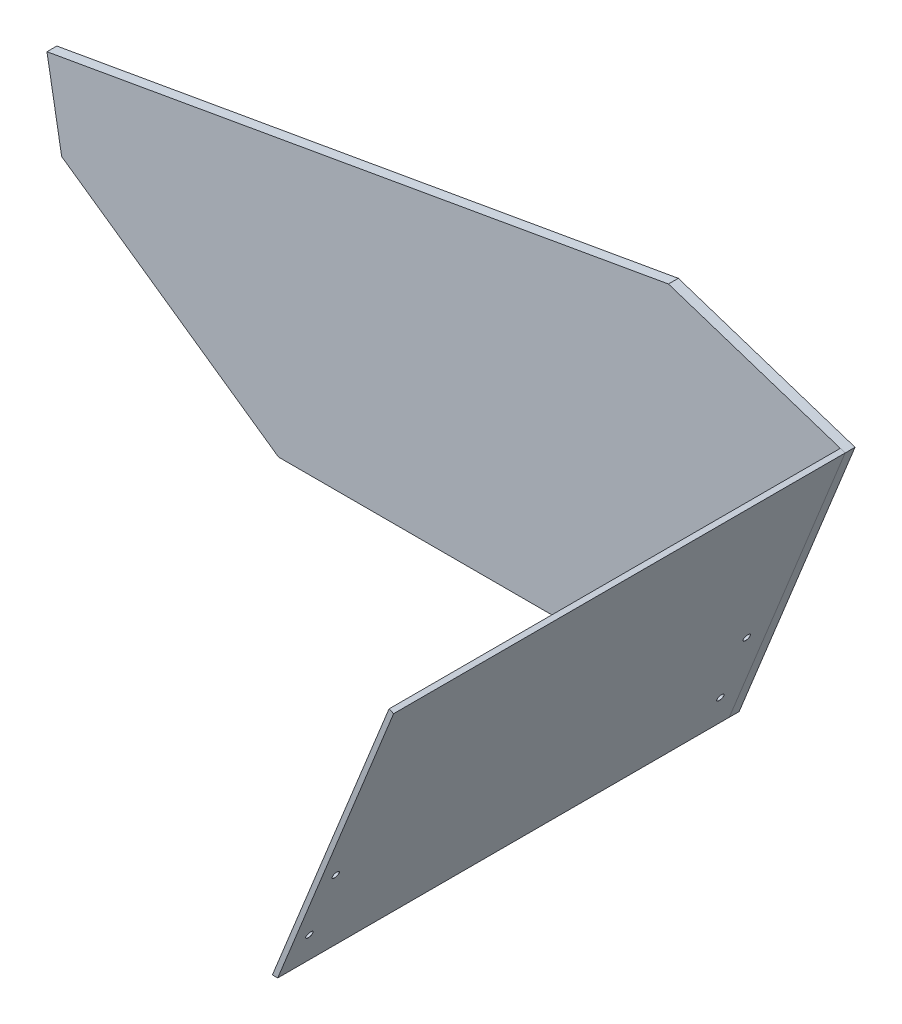
SolidWorks part; units mm, degrees
material "Melamine"
ref_plane "Front Plane" through (0, 0, 0) normal (0, 0, 1) x (1, 0, 0)
ref_plane "Top Plane" through (0, 0, 0) normal (0, 1, 0) x (1, 0, 0)
ref_plane "Right Plane" through (0, 0, 0) normal (1, 0, 0) x (0, 0, -1)
ref_axis "Axis1" through (0, 0, -14.8175) along (0, 0, 1)
sketch "Sketch1" plane through (0, 0, 0) normal (0, 0, 1) x (1, 0, 0)
  line L0 (-140, 0) -> (140, 0) construction
  line L1 (-140, 0) -> (-303.8304, 114.7153) construction
  line L4 (-151.0709, 0) -> (-307.4726, 109.5137) construction
  line L5 (-307.4726, 109.5137) -> (-303.8304, 114.7153) construction
  line L11 (140, 0) -> (143.4243, 0)
  line L12 (140, 0) -> (214.9213, 185.4368) construction
  line L14 (143.4243, 0) -> (217.8651, 184.2474)
  line L15 (217.8651, 184.2474) -> (214.9213, 185.4368)
  line L16 (214.9213, 185.4368) -> (140, 0)
  line L17 (-140, 0) -> (-151.0709, 0) construction
  point P4 (0, 0)
  dimension "D1" = 35
  dimension "D2" = 280
  dimension "D4" = 200
  dimension "D6" = 6.35
  dimension "D7" = 68
  dimension "D8" = 200
  dimension "D9" = 3.175
extrude "Boss-Extrude1" add sketch "Sketch1" along normal blind 290
sketch "Sketch2" plane through (0, 0, 0) normal (0, 0, 1) x (1, 0, 0)
  line L1 (-294.7779, 151.108) -> (104.3699, 221.4886)
  line L3 (143.4243, 0) -> (-146.0709, 0)
  line L4 (-146.0709, 0) -> (-285.3267, 97.508) construction
  line L5 (143.4243, 0) -> (217.8651, 184.2474)
  line L7 (-285.3267, 97.508) -> (-294.7779, 151.108)
  line L8 (-285.3267, 97.508) -> (-281.6845, 102.7096) construction
  line L9 (217.8651, 184.2474) -> (104.3699, 221.4886)
  line L10 (143.4243, 0) -> (104.3699, 221.4886) construction
  line L11 (-285.3267, 97.508) -> (-146.0709, 0)
  line L13 (-146.0709, 0) -> (-135, 0) construction
  line L14 (-285.3267, 97.508) -> (-146.0709, 0) construction
  line L15 (-281.6845, 102.7096) -> (-135, 0) construction
  dimension "D1" = 10
  dimension "D2" = 200
  dimension "D3" = 6.35
  dimension "D4" = 35
  dimension "D5" = 170
  dimension "D6" = 275
extrude "Boss-Extrude2" add sketch "Sketch2" against normal blind 6.35 separate body
ref_plane "HOLDING PLANE" through (0, 0, 0) normal (0.9848, 0.1736, 0) x (0, 0, 1)
ref_point "Walls Center"
hole_wizard "M4 Clearance Hole1" positions "Sketch3" profile "Sketch4" hole size "M4" standard "ANSI Metric" end condition through all
sketch "Sketch3" plane through (123.2976, -49.8155, 0) normal (0.9272, -0.3746, 0) x (0, 0, -1)
  line L0 (0, 53.7277) -> (0, 252.4449) construction
  line L1 (-290, 53.7277) -> (0, 53.7277) construction
  point P0 (-279, 123.7277)
  point P3 (-279, 78.7277)
  point P6 (-15, 123.7277)
  point P9 (-15, 78.7277)
  point P15 (-15, 123.7277)
  point P16 (0, 0)
  point P17 (-20.032, 78.7277)
  point P22 (0, 0)
  point P23 (0, 0)
  point P24 (-15, 123.7277)
  point P25 (-15, 78.7277)
  point P26 (-279, 78.7277)
  point P27 (-15, 78.7277)
  point P28 (-15, 123.7277)
  point P29 (0, 0)
  dimension "D1" = 15
  dimension "D2" = 25
sketch "Sketch4" plane through (169.6468, 64.9029, 279) normal (0, 0, 1) x (0.3746, 0.9272, 0)
  line L0 (0, 0) -> (0, 489.2651)
  line L1 (0, 489.2651) -> (2.25, 489.2651)
  line L2 (2.25, 489.2651) -> (2.25, 0.025)
  line L3 (2.25, 0.025) -> (2.275, 0)
  line L5 (2.275, 0) -> (0, 0)
  line L6 (-2.25, 0.025) -> (-2.275, 0) construction
  line L11 (0, -6.35) -> (0, 107.95) construction
  dimension "Thru Hole Dia." = 4.5
  dimension "Thru Hole Depth" = 489.2651
  dimension "Near C'Sink Dia." = 4.55
  dimension "Near C'Sink Angle" = 90
